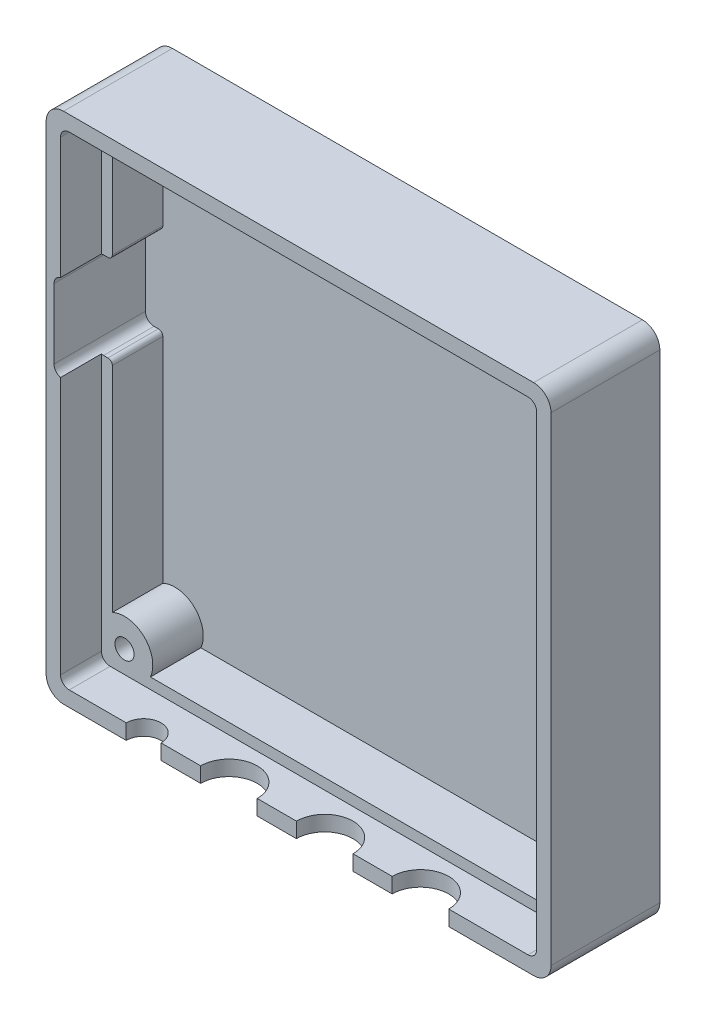
SolidWorks part; units mm, degrees
ref_plane "Front Plane" through (0, 0, 0) normal (0, 0, 1) x (1, 0, 0)
ref_plane "Top Plane" through (0, 0, 0) normal (0, 1, 0) x (1, 0, 0)
ref_plane "Right Plane" through (0, 0, 0) normal (1, 0, 0) x (0, 0, -1)
sketch "Sketch1" plane through (0, 0, 0) normal (0, 0, 1) x (1, 0, 0)
  line L0 (-29, 0) -> (29, 0) construction
  line L1 (-27, -29.5) -> (27, -29.5)
  line L2 (-29, -27.5) -> (-29, 27.5)
  line L3 (-27, 29.5) -> (27, 29.5)
  line L4 (29, -27.5) -> (29, 27.5)
  line L5 (0, -29.5) -> (0, 29.5) construction
  arc A0 (-29, -27.5) -> (-27, -29.5) centre (-27, -27.5) ccw
  arc A1 (27, -29.5) -> (29, -27.5) centre (27, -27.5) ccw
  arc A2 (29, 27.5) -> (27, 29.5) centre (27, 27.5) ccw
  arc A3 (-27, 29.5) -> (-29, 27.5) centre (-27, 27.5) ccw
  point P7 (-28.1524, -26.5589)
  dimension "D1" = 2
  dimension "D2" = 58
  dimension "D3" = 59
extrude "Gehäusekorpus" add sketch "Sketch1" along normal blind 12.5
sketch "Sketch3" plane through (0, 0, 12.5) normal (0, 0, 1) x (1, 0, 0)
  line L0 (0, 26.5) -> (0, -26.5) construction
  line L1 (-25.1, 26.5) -> (21.7213, 26.5)
  line L2 (-26.1, 25.5) -> (-26.1, 13.3)
  line L3 (-21.7213, -26.5) -> (25.1, -26.5)
  line L4 (26.1, 22.267) -> (26.1, -25.5)
  line L5 (26.1, 0) -> (-26.1, 0) construction
  line L6 (-26.1, 2.3) -> (-26.1, -22.267)
  line L7 (-26.6, 12.8) -> (-27.1, 12.8)
  line L9 (-26.6, 2.8) -> (-27.1, 2.8)
  line L10 (-28.1, 11.8) -> (-28.1, 3.8)
  arc A1 (25.1, -26.5) -> (26.1, -25.5) centre (25.1, -25.5) ccw
  arc A3 (-25.1, 26.5) -> (-26.1, 25.5) centre (-25.1, 25.5) ccw
  arc A4 (-28.1, 3.8) -> (-27.1, 2.8) centre (-27.1, 3.8) ccw
  arc A5 (-28.1, 11.8) -> (-27.1, 12.8) centre (-27.1, 11.8) cw
  arc A6 (-26.1, 2.3) -> (-26.6, 2.8) centre (-26.6, 2.3) ccw
  arc A7 (-26.1, 13.3) -> (-26.6, 12.8) centre (-26.6, 13.3) cw
  arc A8 (21.7213, 26.5) -> (26.1, 22.267) centre (24.7, 25.2) ccw
  circle A9 centre (24.7, 25.2) radius 1.1 construction
  arc A10 (-21.7213, -26.5) -> (-26.1, -22.267) centre (-24.7, -25.2) ccw
  circle A11 centre (-24.7, -25.2) radius 1.1 construction
  point P2 (0, 0)
  point P5 (0, 0)
  point P10 (-26.1, -26.5)
  point P18 (-26.1, 26.5)
  point P25 (-28.1, 2.8)
  point P28 (-28.1, 12.8)
  point P31 (-26.1, 2.8)
  point P41 (0, 0)
  point P42 (0, 0)
  dimension "D3" = 46.8213
  dimension "D7" = 1
  dimension "D8" = 0.5
  dimension "D9" = 12.2
  dimension "D12" = 2.2
  dimension "D16" = 2.2
  dimension "D20" = 3.25
  dimension "D21" = 3.25
  dimension "D1" = 53
  dimension "D2" = 52.2
  dimension "D4" = 10
  dimension "D5" = 2
  dimension "D6" = 29.3
  dimension "D10" = 25.2
  dimension "D11" = 24.7
  dimension "D13" = 25.2
  dimension "D14" = 24.7
  dimension "D17" = 24.567
  dimension "D18" = 47.767
  dimension "D19" = 46.8213
extrude "Gehäuseaushöhlung" cut sketch "Sketch3" against normal offset from surface (10.5 mm away) 2 up to face at (0, 0, 0)
sketch "Sketch4" plane through (0, 0, 12.5) normal (0, 0, 1) x (1, 0, 0)
  line L0 (0, 27.75) -> (0, -27.75) construction
  line L1 (-26.35, 27.75) -> (26.35, 27.75)
  line L2 (-27.35, 26.75) -> (-27.35, -26.75)
  line L3 (-26.35, -27.75) -> (26.35, -27.75)
  line L4 (27.35, 26.75) -> (27.35, -26.75)
  arc A0 (-27.35, -26.75) -> (-26.35, -27.75) centre (-26.35, -26.75) ccw
  arc A1 (26.35, -27.75) -> (27.35, -26.75) centre (26.35, -26.75) ccw
  arc A2 (27.35, 26.75) -> (26.35, 27.75) centre (26.35, 26.75) ccw
  arc A3 (-26.35, 27.75) -> (-27.35, 26.75) centre (-26.35, 26.75) ccw
  point P9 (-27.35, -27.75)
  point P14 (27.35, 27.75)
  point P17 (-27.35, 27.75)
  dimension "D3" = 1
  dimension "D1" = 54.7
  dimension "D2" = 55.5
extrude "Platinenhalterung" cut sketch "Sketch4" against normal blind 4.7
sketch "Sketch8" plane through (0, 0, 7.8) normal (0, 0, 1) x (1, 0, 0)
  circle A1 centre (-24.7, -25.2) radius 1.1
  circle A2 centre (24.7, 25.2) radius 1.1
  point P4 (24.5783, 25.1318)
  dimension "D1" = 2.2
  dimension "D2" = 24.7
  dimension "D6" = 2.2
  dimension "D3" = 25.2
  dimension "D4" = 24.7
  dimension "D5" = 25.2
extrude "Schraublöcher" cut sketch "Sketch8" against normal through all
sketch "Sketch9" plane through (0, 0, 0) normal (0, 0, 1) x (1, 0, 0)
  line L0 (26.35, 27.75) -> (-26.35, 27.75) construction
  line L1 (27.1826, 25.2) -> (25.9413, 27.35)
  line L2 (25.9413, 27.35) -> (23.4587, 27.35)
  line L3 (23.4587, 27.35) -> (22.2174, 25.2)
  line L4 (22.2174, 25.2) -> (23.4587, 23.05)
  line L5 (23.4587, 23.05) -> (25.9413, 23.05)
  line L6 (25.9413, 23.05) -> (27.1826, 25.2)
  line L7 (-22.2174, -25.2) -> (-23.4587, -23.05)
  line L8 (-23.4587, -23.05) -> (-25.9413, -23.05)
  line L9 (-25.9413, -23.05) -> (-27.1826, -25.2)
  line L10 (-27.1826, -25.2) -> (-25.9413, -27.35)
  line L11 (-25.9413, -27.35) -> (-23.4587, -27.35)
  line L12 (-23.4587, -27.35) -> (-22.2174, -25.2)
  line L13 (-26.35, -27.75) -> (26.35, -27.75) construction
  circle A0 centre (24.7, 25.2) radius 2.15 construction
  circle A1 centre (-24.7, -25.2) radius 2.15 construction
  dimension "D1" = 4.3
  dimension "D2" = 4.3
extrude "Schraubenmutter_Ausnehmungen" cut sketch "Sketch9" along normal blind 3
sketch "Sketch10" plane through (0, -29.5, 0) normal (0, -1, 0) x (1, 0, 0)
  line L0 (-27, 12.5) -> (27, 12.5) construction
  line L1 (-27.1, 12.5) -> (27.1, 12.5) construction
  circle A0 centre (-8, 12.5) radius 3.25
  circle A1 centre (3, 12.5) radius 3.25
  circle A2 centre (14, 12.5) radius 3.25
  circle A3 centre (-17.8, 12.5) radius 2
  dimension "D1" = 6.5
  dimension "D2" = 6.5
  dimension "D3" = 6.5
  dimension "D4" = 4
  dimension "D5" = 11
  dimension "D6" = 11
  dimension "D7" = 9.8
  dimension "D8" = 54.2
  dimension "D9" = 9.3
  dimension "D10" = 12.5
  dimension "D11" = 27.1
extrude "Button_Ausnehmungen" cut sketch "Sketch10" against normal blind 3
equation "\"D151.000000mm\"=51"
equation "\"D250.000000mm\"=50"
